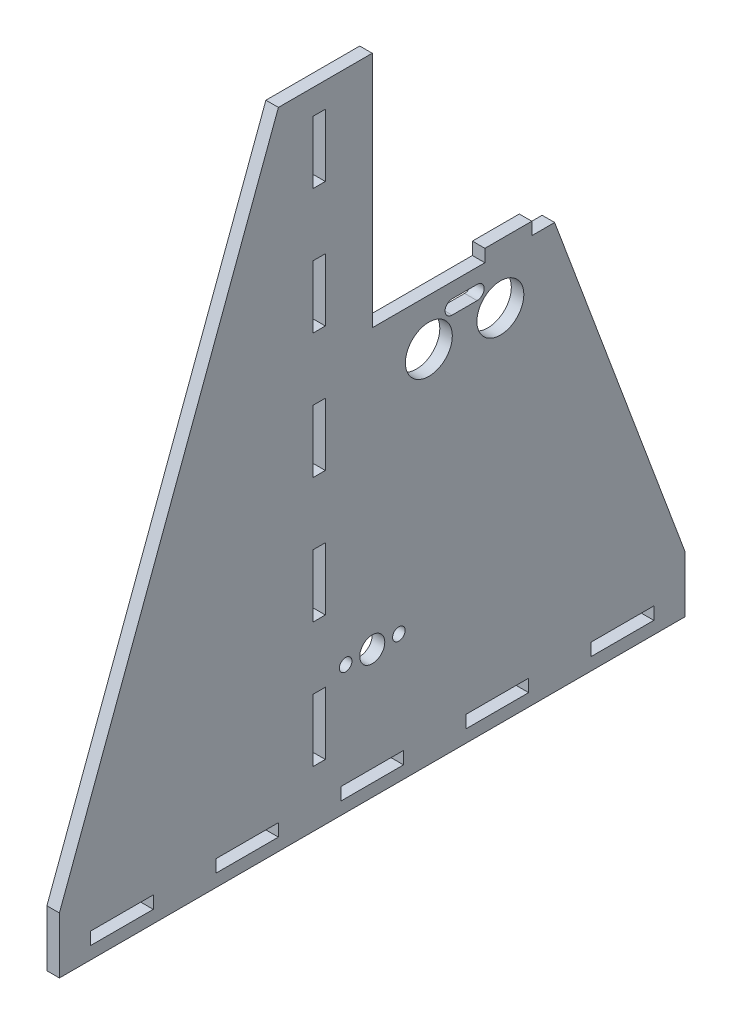
SolidWorks part; units mm, degrees
ref_plane "Přední rovina" through (0, 0, 0) normal (0, 0, 1) x (1, 0, 0)
ref_plane "Horní rovina" through (0, 0, 0) normal (0, 1, 0) x (1, 0, 0)
ref_plane "Pravá rovina" through (0, 0, 0) normal (1, 0, 0) x (0, 0, -1)
sketch "Skica1" plane through (0, 0, 0) normal (1, 0, 0) x (0, 0, -1)
  line L0 (0, 0) -> (0, 200)
  line L1 (-100, 0) -> (100, 0)
  line L2 (-100, 0) -> (-100, 206)
  line L3 (-100, 206) -> (100, 206)
  line L4 (100, 0) -> (100, 206)
  line L5 (-90, 4) -> (-70, 4)
  line L6 (-90, 4) -> (-90, 8)
  line L7 (-90, 8) -> (-70, 8)
  line L8 (-70, 4) -> (-70, 8)
  line L9 (-50, 4) -> (-30, 4)
  line L10 (-50, 4) -> (-50, 8)
  line L11 (-50, 8) -> (-30, 8)
  line L12 (-30, 4) -> (-30, 8)
  line L13 (-10, 4) -> (10, 4)
  line L14 (-10, 4) -> (-10, 8)
  line L15 (-10, 8) -> (10, 8)
  line L16 (10, 4) -> (10, 8)
  line L17 (50, 8) -> (30, 8)
  line L18 (30, 4) -> (30, 8)
  line L19 (50, 4) -> (30, 4)
  line L20 (50, 4) -> (50, 8)
  line L21 (90, 8) -> (70, 8)
  line L22 (70, 4) -> (70, 8)
  line L23 (90, 4) -> (70, 4)
  line L24 (90, 4) -> (90, 8)
  line L25 (-8.5, 41) -> (0, 41)
  line L26 (0, 200) -> (0, 206)
  line L27 (-15, 18) -> (-19, 18)
  line L28 (-15, 18) -> (-15, 38)
  line L29 (-15, 38) -> (-19, 38)
  line L30 (-19, 18) -> (-19, 38)
  line L31 (-15, 58) -> (-19, 58)
  line L32 (-15, 58) -> (-15, 78)
  line L33 (-15, 78) -> (-19, 78)
  line L34 (-19, 58) -> (-19, 78)
  line L35 (-15, 98) -> (-19, 98)
  line L36 (-15, 98) -> (-15, 118)
  line L37 (-15, 118) -> (-19, 118)
  line L38 (-19, 98) -> (-19, 118)
  line L39 (-15, 138) -> (-19, 138)
  line L40 (-15, 138) -> (-15, 158)
  line L41 (-15, 158) -> (-19, 158)
  line L42 (-19, 138) -> (-19, 158)
  line L43 (-15, 178) -> (-19, 178)
  line L44 (-15, 178) -> (-15, 198)
  line L45 (-15, 198) -> (-19, 198)
  line L46 (-19, 178) -> (-19, 198)
  line L47 (-30, 206) -> (-100, 18)
  line L48 (100, 18) -> (30, 206)
  line L49 (58.2979, 130) -> (0, 130)
  line L50 (25.5223, 123) -> (33.5223, 123) construction
  line L51 (36, 130) -> (51, 130)
  line L52 (36, 130) -> (36, 134)
  line L53 (36, 134) -> (51, 134)
  line L54 (51, 130) -> (51, 134)
  line L55 (25.5223, 125.25) -> (33.5223, 125.25)
  line L56 (25.5223, 120.75) -> (33.5223, 120.75)
  circle A0 centre (0, 41) radius 4
  circle A1 centre (-8.5, 41) radius 2
  circle A2 centre (8.5, 41) radius 2
  circle A3 centre (18.0923, 115) radius 7.5
  circle A4 centre (40.9523, 115) radius 7.5
  arc A5 (25.5223, 125.25) -> (25.5223, 120.75) centre (25.5223, 123) ccw
  arc A6 (33.5223, 120.75) -> (33.5223, 125.25) centre (33.5223, 123) ccw
  point P19 (-30, 6)
  point P20 (-70, 6)
  point P21 (-80, 8)
  point P56 (-17, 178)
  point P57 (-30, 206)
  point P59 (30, 206)
  point P76 (29.5223, 123)
  dimension "D13" = 8
  dimension "D15" = 4
  dimension "D31" = 15
  dimension "D33" = 8
  dimension "D37" = 8
  dimension "D1" = 200
  dimension "D2" = 100
  dimension "D3" = 206
  dimension "D4" = 20
  dimension "D5" = 10
  dimension "D6" = 20
  dimension "D7" = 20
  dimension "D8" = 20
  dimension "D9" = 20
  dimension "D10" = 4
  dimension "D11" = 4
  dimension "D12" = 0
  dimension "D14" = 8.5
  dimension "D16" = 37
  dimension "D17" = 10
  dimension "D18" = 20
  dimension "D19" = 20
  dimension "D20" = 20
  dimension "D21" = 20
  dimension "D22" = 20
  dimension "D23" = 20
  dimension "D24" = 20
  dimension "D25" = 20
  dimension "D26" = 20
  dimension "D27" = 4
  dimension "D28" = 15
  dimension "D29" = 30
  dimension "D30" = 22.86
  dimension "D32" = 74
  dimension "D34" = 36
  dimension "D35" = 15
  dimension "D36" = 73.2979
  dimension "D38" = 11.43
  dimension "D39" = 8
  dimension "D40" = 4.5
  dimension "D41" = 4
extrude "Přidat vysunutím1" add sketch "Skica1" along normal blind 4 contours L14 L15 L0 L3 L2 L1 L13 L12 L9 L10 L11 L8 L5 L6 L7 | L16 L13 L0 L1 L4 L3 L15 L24 L23 L22 L21 L20 L19 L18 L17 | L53 L54 L51 L52 region at (0, 84.6432, 38.0192) region at (0, 57.7569, -42.6092)
